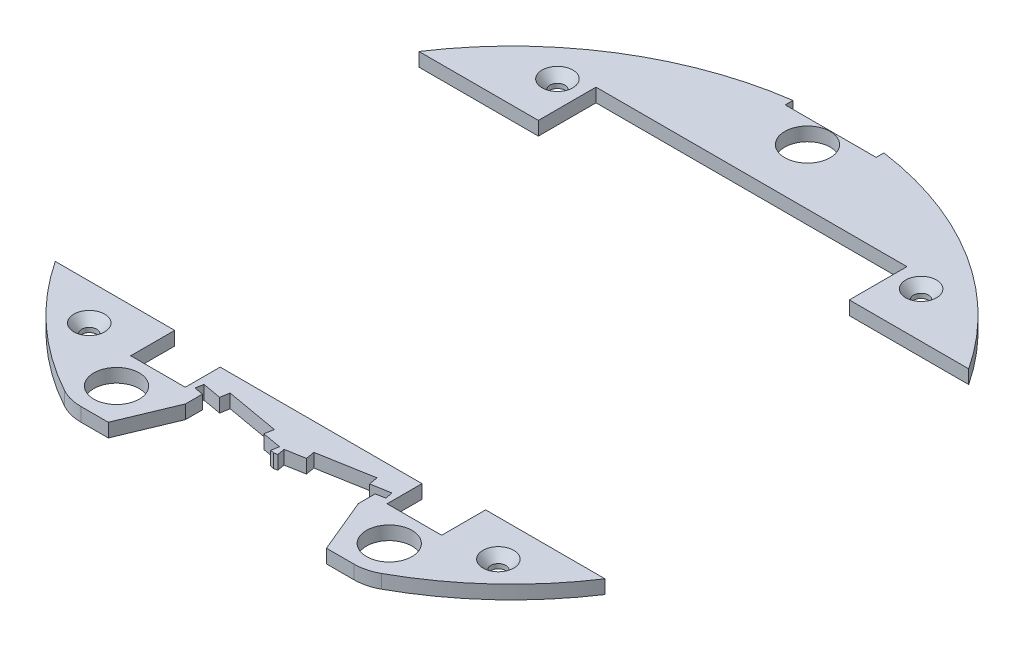
SolidWorks part; units mm, degrees
material "ABS"
ref_plane "Front Plane" through (0, 0, 0) normal (0, 0, 1) x (1, 0, 0)
ref_plane "Top Plane" through (0, 0, 0) normal (0, 1, 0) x (1, 0, 0)
ref_plane "Right Plane" through (0, 0, 0) normal (1, 0, 0) x (0, 0, -1)
sketch "Sketch1" plane through (0, 0, 0) normal (0, 1, 0) x (1, 0, 0)
  line L0 (-30.03, -64.8129) -> (30.03, -64.8129)
  line L1 (0, -85) -> (0, 0) construction
  line L2 (0, -85) -> (32.4891, -64.8129) construction
  arc A0 (34.8348, -63.5829) -> (-34.8348, -63.5829) centre (0, 0) ccw
  circle A1 centre (0, -85) radius 38.25 construction
  arc A2 (30.03, -64.8129) -> (34.8348, -63.5829) centre (30.03, -54.8129) ccw
  arc A3 (-30.03, -64.8129) -> (-34.8348, -63.5829) centre (-30.03, -54.8129) cw
  dimension "D1" = 145
  dimension "D2" = 76.5
  dimension "D4" = 10
  dimension "D3" = 85
extrude "Boss-Extrude1" add sketch "Sketch1" along normal blind 3
sketch "Sketch2" plane through (0, 3, 0) normal (0, 1, 0) x (1, 0, 0)
  line L5 (22.2, -49.6757) -> (22.2, -42)
  line L6 (22.2, -42) -> (-22.2, -42)
  line L7 (-22.2, -42) -> (-22.2, -49.6757)
  line L8 (22.2, 49.6757) -> (22.2, 45.5)
  line L9 (-34.2, -49.6757) -> (-22.2, -49.6757) construction
  line L10 (-34.2, -49.6757) -> (-34.2, 49.6757) construction
  line L11 (-34.2, 49.6757) -> (-22.2, 49.6757) construction
  line L19 (34.2, 49.6757) -> (22.2, 49.6757) construction
  line L20 (34.2, -49.6757) -> (34.2, 49.6757) construction
  line L21 (34.2, -49.6757) -> (22.2, -49.6757) construction
  line L22 (22.2, 45.5) -> (-22.2, 45.5)
  line L23 (-22.2, 45.5) -> (-22.2, 49.6757)
  line L35 (-34.2, -49.6757) -> (-22.2, -49.6757)
  line L36 (-34.2, -49.6757) -> (-34.2, 49.6757)
  line L37 (-34.2, 49.6757) -> (-22.2, 49.6757)
  line L55 (34.2, 49.6757) -> (22.2, 49.6757)
  line L56 (34.2, -49.6757) -> (34.2, 49.6757)
  line L57 (34.2, -49.6757) -> (22.2, -49.6757)
  dimension "D1" = 42
  dimension "D2" = 45.5
extrude "Cut-Extrude1" cut sketch "Sketch2" against normal through all contours L55 L37 L36 L35 L7 L6 L5 L57 L56 region at (0, 3, -1.0844)
sketch "Sketch3" plane through (0, 3, 0) normal (0, 1, 0) x (1, 0, 0)
  line L0 (-34.2, 40) -> (-34.2, -40)
  line L1 (-72.5, -40) -> (-34.2, -40)
  line L2 (-72.5, -40) -> (-72.5, 40)
  line L3 (-72.5, 40) -> (-34.2, 40)
  line L4 (72.5, -40) -> (72.5, 40)
  line L5 (-72.5, -40) -> (72.5, 40) construction
  line L6 (-72.5, 40) -> (72.5, -40) construction
  line L7 (-34.2, -49.6757) -> (-34.2, 49.6757) construction
  line L8 (34.2, 40) -> (34.2, -40)
  line L9 (34.2, -49.6757) -> (34.2, 49.6757) construction
  line L10 (34.2, 40) -> (72.5, 40)
  line L11 (34.2, -40) -> (72.5, -40)
  arc A0 (34.8348, -63.5829) -> (-34.8348, -63.5829) centre (0, 0) ccw construction
  point P0 (0, 0)
  dimension "D1" = 80
extrude "Cut-Extrude2" cut sketch "Sketch3" against normal through all
sketch "Sketch4" plane through (0, 3, 0) normal (0, 1, 0) x (1, 0, 0)
  line L0 (-20.9838, -48.7531) -> (-0.7952, -52.3129)
  line L1 (20.9838, -48.7531) -> (20.6886, -47.0789)
  line L2 (0.7952, -52.3129) -> (0.5, -50.6387)
  line L3 (20.6886, -47.0789) -> (0.5, -50.6387)
  line L4 (0, 0) -> (0, -64.8129) construction
  line L5 (-30.03, -64.8129) -> (30.03, -64.8129) construction
  line L6 (-20.6886, -47.0789) -> (-0.5, -50.6387)
  line L7 (-0.7952, -52.3129) -> (-0.5, -50.6387)
  line L8 (-20.9838, -48.7531) -> (-20.6886, -47.0789)
  line L14 (20.9838, -48.7531) -> (0.7952, -52.3129)
  dimension "D1" = 1.7
  dimension "D2" = 20.5
  dimension "D3" = 10
  dimension "D4" = 12.5
  dimension "D5" = 0.5
extrude "Cut-Extrude3" cut sketch "Sketch4" against normal through all
sketch "Sketch5" plane through (0, 3, 0) normal (0, 1, 0) x (1, 0, 0)
  line L0 (-19, -64.8129) -> (-19, -49.1029)
  line L1 (19, -49.1029) -> (0, -52.4531)
  line L2 (0, -52.4531) -> (-19, -49.1029)
  line L3 (-20.9838, -48.7531) -> (-0.7952, -52.3129) construction
  line L4 (0.7952, -52.3129) -> (20.9838, -48.7531) construction
  line L5 (16.5031, -47.8169) -> (4.6854, -49.9007)
  line L6 (16.5031, -47.8169) -> (16.1558, -45.8473)
  line L7 (4.6854, -49.9007) -> (4.3381, -47.9311)
  line L8 (16.1558, -45.8473) -> (4.3381, -47.9311)
  line L9 (20.6886, -47.0789) -> (0.5, -50.6387) construction
  line L10 (0, 0) -> (0, -49.1029) construction
  line L11 (19, -64.8129) -> (19, -49.1029)
  line L13 (-16.1558, -45.8473) -> (-4.3381, -47.9311)
  line L14 (-4.6854, -49.9007) -> (-4.3381, -47.9311)
  line L15 (-16.5031, -47.8169) -> (-16.1558, -45.8473)
  line L16 (-16.5031, -47.8169) -> (-4.6854, -49.9007)
  line L22 (-30.03, -64.8129) -> (30.03, -64.8129) construction
  line L23 (19, -49.1029) -> (-19, -49.1029) construction
  line L25 (-19, -64.8129) -> (19, -64.8129)
  point P14 (10.5943, -48.8588)
  point P15 (10.5943, -48.8588)
  dimension "D1" = 12
  dimension "D2" = 38
  dimension "D4" = 2
extrude "Cut-Extrude4" cut sketch "Sketch5" against normal through all
sketch "Sketch6" plane through (0, 3, 0) normal (0, 1, 0) x (1, 0, 0)
  line L1 (34.2, 49.6757) -> (-34.2, 49.6757)
  line L2 (34.2, 49.6757) -> (34.2, 52.6757)
  line L3 (34.2, 52.6757) -> (-34.2, 52.6757)
  line L4 (-34.2, 49.6757) -> (-34.2, 52.6757)
  dimension "D1" = 3
extrude "Cut-Extrude5" cut sketch "Sketch6" against normal through all body kept at (60.4669, 0, -40)
sketch "Sketch7" plane through (0, 3, 0) normal (0, 1, 0) x (1, 0, 0)
  line L0 (0, 0) -> (0, -31.2827) construction
  circle A0 centre (-30, -57) radius 5
  circle A4 centre (30, -57) radius 5
  dimension "D1" = 10
  dimension "D2" = 30
  dimension "D3" = 57
extrude "Cut-Extrude6" cut sketch "Sketch7" against normal through all
sketch "Sketch11" plane through (0, 3, 0) normal (0, 1, 0) x (1, 0, 0)
  line L0 (0, 0) -> (0, 65) construction
  circle A0 centre (0, 65) radius 5
  dimension "D2" = 10
  dimension "D1" = 65
extrude "Cut-Extrude10" cut sketch "Sketch11" against normal through all
sketch "Sketch13" plane through (0, 3, 0) normal (0, 1, 0) x (1, 0, 0)
  line L0 (19, -52.8129) -> (24, -64.8129)
  line L1 (19, -64.8129) -> (19, -49.1029) construction
  line L2 (19, -64.8129) -> (30.03, -64.8129) construction
  line L3 (24, -64.8129) -> (19, -64.8129)
  line L4 (19, -64.8129) -> (19, -52.8129)
  line L5 (0, 0) -> (0, -25.0729) construction
  line L6 (-19, -64.8129) -> (-19, -52.8129)
  line L7 (-24, -64.8129) -> (-19, -64.8129)
  line L8 (-19, -52.8129) -> (-24, -64.8129)
  dimension "D1" = 12
  dimension "D2" = 5
extrude "Cut-Extrude11" cut sketch "Sketch13" against normal through all
sketch "Sketch14" plane through (0, 3, 0) normal (0, 1, 0) x (1, 0, 0)
  line L1 (0, 0) -> (0, -20.685) construction
  circle A0 centre (45, -48) radius 1.65
  circle A1 centre (-45, -48) radius 1.65
  circle A2 centre (40, 50) radius 1.65
  circle A3 centre (-40, 50) radius 1.65
  dimension "D3" = 3.3
  dimension "D1" = 45
  dimension "D2" = 48
  dimension "D4" = 40
  dimension "D5" = 50
extrude "Cut-Extrude12" cut sketch "Sketch14" against normal through all
sketch "Sketch15" plane through (0, 3, 0) normal (0, 1, 0) x (1, 0, 0)
  line L1 (10, 71.807) -> (-10, 71.807)
  line L2 (10, 71.807) -> (10, 70.107)
  line L3 (10, 70.107) -> (-10, 70.107)
  line L4 (-10, 71.807) -> (-10, 70.107)
  arc A0 (60.4669, 40) -> (-60.4669, 40) centre (0, 0) ccw construction
  dimension "D1" = 20
  dimension "D2" = 1.7
extrude "Cut-Extrude13" cut sketch "Sketch15" against normal blind 10
chamfer "Chamfer1" distance 2 angle 41 2 edges at (-45, 3, 46.35) (45, 3, 49.65) first distance on face at (-45, 0, 46.35) first distance on face at (45, 0, 49.65)
chamfer "Chamfer2" distance 2 angle 41 2 edges at (-40, 3, -51.65) (40, 3, -48.35) first distance on face at (-40, 0, -51.65) first distance on face at (40, 0, -48.35)
equation "\"smallPulleyTeeth\"= 30"
equation "\"largePulleyTeeth\"= 30"
equation "\"eighthThick\"= 3.0mm"
equation "\"sixteenthThick\"= 1.7mm"
equation "\"quarterThick\"=6.0mm"
equation "\"OD\"= 145mm"
equation "\"puckAngle\"= 60.5deg"
equation "\"puckDiam\"= 76.5mm"
equation "\"axlePress\"= 5.9mm"
equation "\"press\"= 0.2mm"
equation "\"wheelClear\"= 0.3mm"
equation "\"10-32clear\"= 4.8mm"
equation "\"6-32clear\"= 3.3mm"
equation "\"8-32clear\"= 4.0mm"
equation "\"4-40clear\"= 3.0mm"
equation "\"wheelHeight\"= 22mm"
equation "\"wheelWell\"= 65mm"
equation "\"D1@Sketch1\"=\"OD\""
equation "\"D1@Boss-Extrude1\"=\"eighthThick\""
equation "\"D2@Sketch1\"=\"puckDiam\""
equation "\"puckDist\"= 85mm"
equation "\"scoopFillet\"= 5mm"
equation "\"10-32tap\"= 4.45mm"
equation "\"ledSmall\"= 3.1mm"
equation "\"ledLarge\"= 4.2mm"
equation "\"ledLength\"= 4.2mm"
equation "\"D3@Sketch1\"=\"puckDist\""
equation "\"D1@Sketch6\"=\"eighthThick\""
equation "\"D2@Sketch15\"=\"sixteenthThick\""
